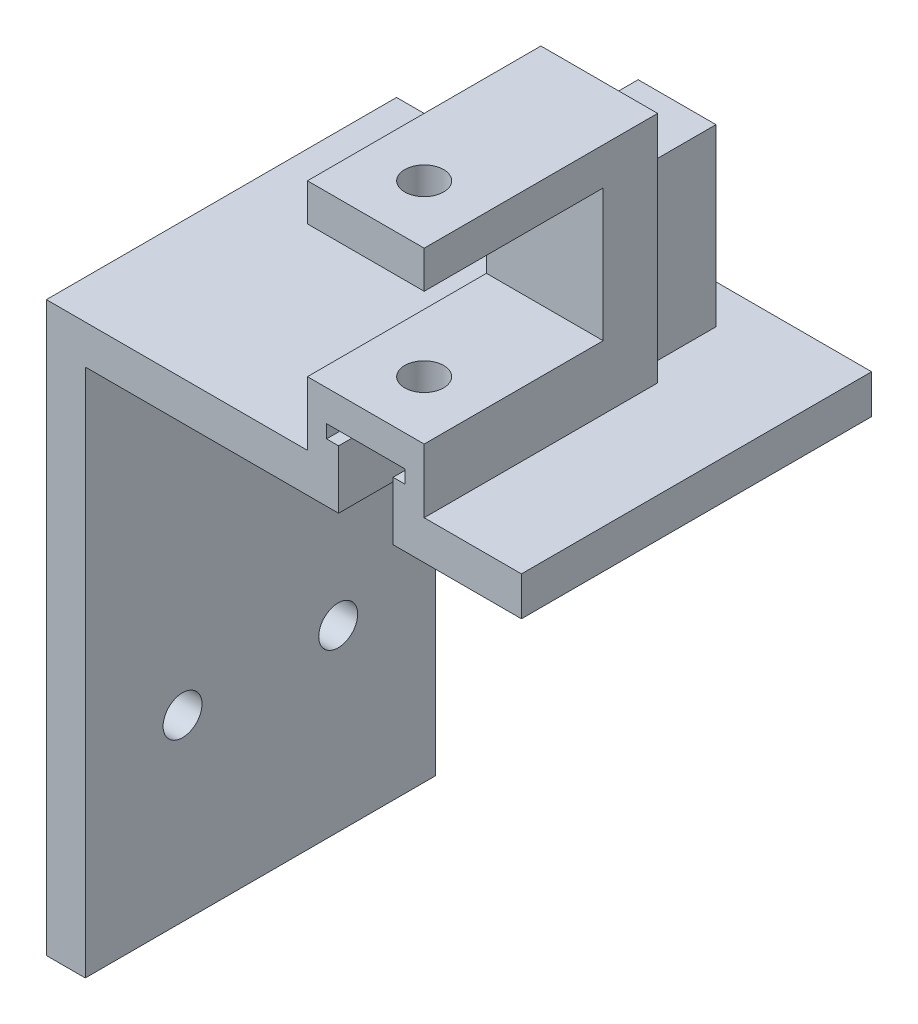
SolidWorks part; units mm, degrees
ref_plane "Front Plane" through (0, 0, 0) normal (0, 0, 1) x (1, 0, 0)
ref_plane "Top Plane" through (0, 0, 0) normal (0, 1, 0) x (1, 0, 0)
ref_plane "Right Plane" through (0, 0, 0) normal (1, 0, 0) x (0, 0, -1)
sketch "Sketch1" plane through (0, 0, 0) normal (0, 1, 0) x (1, 0, 0)
  line L1 (0, 0) -> (61.05, 0)
  line L2 (0, 0) -> (0, 45)
  line L3 (0, 45) -> (61.05, 45)
  line L4 (61.05, 0) -> (61.05, 45)
  dimension "D1" = 61.05
  dimension "D2" = 45
extrude "Boss-Extrude2" add sketch "Sketch1" along normal blind 5
sketch "Sketch2" plane through (0, 5, 0) normal (0, 1, 0) x (1, 0, 0)
  line L1 (36.05, 40) -> (46.05, 40)
  line L2 (36.05, 40) -> (36.05, 30)
  line L3 (36.05, 30) -> (46.05, 30)
  line L4 (46.05, 40) -> (46.05, 30)
  line L5 (61.05, 45) -> (0, 45) construction
  line L6 (61.05, 0) -> (61.05, 45) construction
  dimension "D1" = 10
  dimension "D2" = 10
  dimension "D3" = 5
  dimension "D4" = 15
extrude "Boss-Extrude3" add sketch "Sketch2" along normal blind 22.5
sketch "Sketch3" plane through (0, 0, -40) normal (0, 0, -1) x (-1, 0, 0)
  line L0 (-46.05, 27.5) -> (-46.05, 5) construction
  line L2 (-46.05, 5) -> (-36.05, 5) construction
  circle A0 centre (-41.05, 20.9) radius 4
  dimension "D1" = 8
  dimension "D2" = 5
  dimension "D3" = 15.9
extrude "Cut-Extrude1" cut sketch "Sketch3" against normal blind 8
sketch "Sketch6" plane through (0, 5, 0) normal (0, 1, 0) x (1, 0, 0)
  line L0 (36.05, 30) -> (46.05, 30) construction
  line L1 (33.55, 30) -> (48.55, 30)
  line L2 (33.55, 30) -> (33.55, 0)
  line L3 (33.55, 0) -> (48.55, 0)
  line L4 (48.55, 30) -> (48.55, 0)
  line L5 (0, 0) -> (61.05, 0) construction
  line L6 (61.05, 0) -> (61.05, 45) construction
  dimension "D1" = 0
  dimension "D2" = 0
  dimension "D3" = 12.5
  dimension "D4" = 15
extrude "Boss-Extrude4" add sketch "Sketch6" along normal blind 30
sketch "Sketch7" plane through (0, 0, 0) normal (0, 0, 1) x (1, 0, 0)
  line L0 (48.55, 5) -> (61.05, 5) construction
  line L1 (61.05, 30.2) -> (33.55, 30.2)
  line L2 (61.05, 30.2) -> (61.05, 13.2)
  line L3 (61.05, 13.2) -> (33.55, 13.2)
  line L4 (33.55, 30.2) -> (33.55, 13.2)
  line L5 (61.05, 5) -> (61.05, 0) construction
  line L6 (33.55, 35) -> (33.55, 5) construction
  dimension "D1" = 8.2
  dimension "D2" = 17
  dimension "D3" = 0
  dimension "D4" = 0
extrude "Cut-Extrude3" cut sketch "Sketch7" against normal blind 23
sketch "Sketch8" plane through (0, 35, 0) normal (0, 1, 0) x (1, 0, 0)
  line L0 (61.05, 0) -> (61.05, 45) construction
  line L1 (33.55, 0) -> (48.55, 0) construction
  circle A0 centre (41.05, 7.5) radius 2.5
  dimension "D1" = 5
  dimension "D2" = 20
  dimension "D3" = 7.5
extrude "Cut-Extrude4" cut sketch "Sketch8" against normal through all
sketch "Sketch9" plane through (0, 0, 0) normal (0, -1, 0) x (1, 0, 0)
  line L0 (61.05, -45) -> (0, -45) construction
  line L1 (0, 0) -> (5, 0)
  line L2 (0, 0) -> (0, -45)
  line L3 (0, -45) -> (5, -45)
  line L4 (5, 0) -> (5, -45)
  dimension "D1" = 5
extrude "Boss-Extrude5" add sketch "Sketch9" along normal blind 68
sketch "Sketch10" plane through (0, 0, 0) normal (-1, 0, 0) x (0, 0, 1)
  line L0 (0, 5) -> (0, -68) construction
  line L2 (-45, 5) -> (0, 5) construction
  circle A0 centre (-32.5, -45) radius 2.5
  circle A1 centre (-12.5, -45) radius 2.5
  dimension "D1" = 5
  dimension "D2" = 5
  dimension "D3" = 20
  dimension "D4" = 12.5
  dimension "D5" = 50
  dimension "D6" = 50
extrude "Cut-Extrude5" cut sketch "Sketch10" against normal up to surface (5 mm away) up to face at (5, -34, -22.5)
sketch "Sketch11" plane through (0, 0, 0) normal (0, 0, 1) x (1, 0, 0)
  line L0 (46.1, 7.5) -> (46.1, 9.2)
  line L1 (46.1, 9.2) -> (36, 9.2)
  line L2 (36, 9.2) -> (36, 7.5)
  line L3 (36, 7.5) -> (37.55, 7.5)
  line L4 (37.55, 7.5) -> (37.55, -1.4198)
  line L5 (37.55, -1.4198) -> (44.55, -1.4198)
  line L6 (44.55, -1.4198) -> (44.55, 7.5)
  line L7 (44.55, 7.5) -> (46.1, 7.5)
  line L9 (48.55, 13.2) -> (48.55, 5) construction
  line L11 (33.55, 13.2) -> (48.55, 13.2) construction
  point P9 (46.3341, 2.5104)
  dimension "D1" = 10.1
  dimension "D2" = 1.7
  dimension "D3" = 7
  dimension "D4" = 1.55
  dimension "D7" = 2.45
  dimension "D8" = 4
extrude "Cut-Extrude6" cut sketch "Sketch11" against normal blind 16
